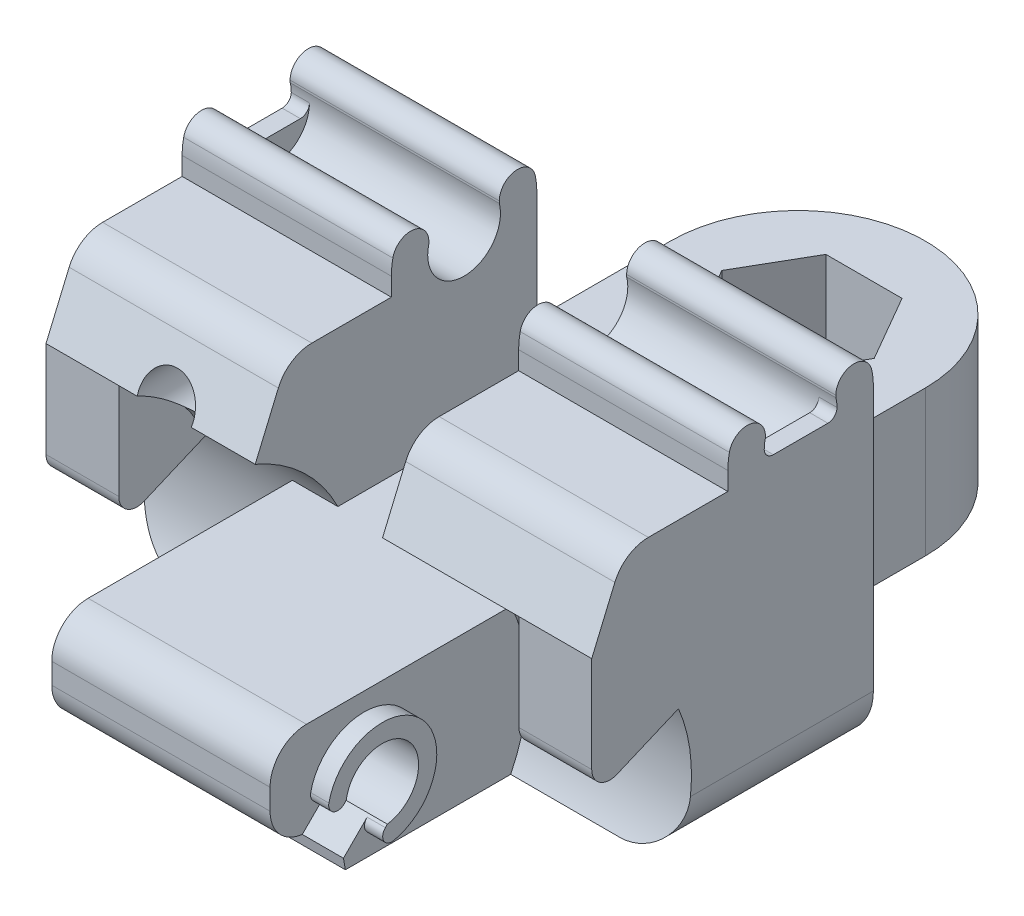
SolidWorks part; units mm, degrees
ref_plane "Front Plane" through (0, 0, 0) normal (0, 0, 1) x (1, 0, 0)
ref_plane "Top Plane" through (0, 0, 0) normal (0, 1, 0) x (1, 0, 0)
ref_plane "Right Plane" through (0, 0, 0) normal (1, 0, 0) x (0, 0, -1)
sketch "Sketch3" plane through (0, 0, 0) normal (1, 0, 0) x (0, 0, -1)
  line L0 (0.2828, -1.9799) -> (-1.9799, 0.2828)
  line L1 (0.2828, -1.9799) -> (-1.1314, -3.3941)
  line L2 (-1.1314, -3.3941) -> (-0.8188, -5.1668)
  line L3 (-0.8188, -5.1668) -> (-3.8071, -8.1551)
  line L4 (-1.9799, 0.2828) -> (-3.3941, -1.1314)
  line L5 (-3.3941, -1.1314) -> (-5.1668, -0.8188)
  line L6 (-5.1668, -0.8188) -> (-8.1551, -3.8071)
  line L7 (-0.8485, -0.8485) -> (0, 0) construction
  line L8 (0, 0) -> (-2, 0) construction
  line L9 (-1.9799, 0.2828) -> (-5.1668, -0.8188) construction
  line L10 (-0.8188, -5.1668) -> (0.2828, -1.9799) construction
  circle A0 centre (0, 0) radius 2
  circle A1 centre (0, 0) radius 8.5 construction
  circle A2 centre (0, 0) radius 9 construction
  circle A3 centre (0, 0) radius 9
  dimension "D1" = 4
  dimension "D2" = 17
  dimension "D3" = 7
  dimension "D4" = 0.5
  dimension "D5" = 2
  dimension "D7" = 3.2
  dimension "D6" = 1.8
  dimension "D8" = 45
  dimension "D9" = 125
extrude "Boss-Extrude1" add sketch "Sketch3" along normal mid plane 12 contours A3 L6 L5 L4 A0 L1 L2 L3 | A3 region at (0, -1.4772, -1.7032)
sketch "Sketch5" plane through (0, 0, 0) normal (1, 0, 0) x (0, 0, -1)
  line L0 (0, 9) -> (29.856, 9)
  line L1 (29.856, 9) -> (29.856, -9)
  line L2 (29.856, -9) -> (0, -9)
  arc A0 (-3.8071, -8.1551) -> (-8.1551, -3.8071) centre (0, 0) ccw construction
  arc A1 (0, -9) -> (0, 9) centre (0, 0) ccw
  dimension "D1" = 29.856
extrude "Boss-Extrude2" add sketch "Sketch5" along normal mid plane 14
sketch "Sketch6" plane through (0, 9, 0) normal (0, 1, 0) x (1, 0, 0)
  line L0 (7, 29.856) -> (-7, 29.856) construction
  circle A0 centre (0, 29.856) radius 7
extrude "Boss-Extrude3" add sketch "Sketch6" against normal up to surface (18 mm away) up to face at (0, -9, -9.952)
sketch "Sketch7" plane through (0, 0, 0) normal (0, 1, 0) x (1, 0, 0)
  circle A0 centre (0, 29.856) radius 4.5
  dimension "D1" = 9
extrude "Boss-Extrude4" add sketch "Sketch7" along normal blind 8 and the other way blind 8
sketch "Sketch8" plane through (0, 9, 0) normal (0, 1, 0) x (1, 0, 0)
  line L0 (6, -9) -> (6, 0) construction
  line L1 (-6, 0) -> (-6, -9) construction
  line L3 (7, 0) -> (7, 29.856) construction
  line L4 (-7, 29.856) -> (-7, 0) construction
  line L5 (-7, 0) -> (-6, 0) construction
  line L6 (6, 0) -> (7, 0) construction
  line L7 (6, -9) -> (6, 0)
  line L8 (-6, 0) -> (-6, -9)
  line L9 (-6, -9) -> (6, -9)
  line L10 (7, 0) -> (7, 29.856)
  line L11 (-7, 29.856) -> (-7, 0)
  line L12 (-7, 0) -> (-6, 0)
  line L13 (6, 0) -> (7, 0)
  arc A0 (7, 29.856) -> (-7, 29.856) centre (0, 29.856) ccw construction
  arc A1 (7, 29.856) -> (-7, 29.856) centre (0, 29.856) ccw
  line M10 (7, 0) -> (7, 29.856)
  arc M11 (7, 29.856) -> (-7, 29.856) centre (0, 29.856) ccw
  line M12 (-7, 29.856) -> (-7, 0)
  line M13 (-7, 0) -> (-6, 0)
  line M14 (-6, 0) -> (6, 0)
  line M15 (6, 0) -> (7, 0)
extrude "Cut-Extrude2" cut sketch "Sketch8" against normal offset from surface (5 mm away) 4 contours M15 M10 M11 M12 M13 M14 | L8 L9 L7 M14 region at (0, 9, 4.5) region at (0, 9, -17.7114) up to plane "Top Plane"
sketch "Sketch9" plane through (0, -9, 0) normal (0, -1, 0) x (1, 0, 0)
  line L7 (6, 0) -> (6, 9)
  line L8 (7, 0) -> (6, 0)
  line L9 (7, -29.856) -> (7, 0)
  line L10 (-7, 0) -> (-7, -29.856)
  line L11 (-6, 0) -> (-7, 0)
  line L12 (-6, 9) -> (-6, 0)
  line L13 (6, 9) -> (-6, 9)
  line L14 (6, 0) -> (6, 9)
  line L15 (7, 0) -> (6, 0)
  line L16 (7, -29.856) -> (7, 0)
  line L17 (-7, 0) -> (-7, -29.856)
  line L18 (-6, 0) -> (-7, 0)
  line L19 (-6, 9) -> (-6, 0)
  line L20 (6, 9) -> (-6, 9)
  arc A1 (-7, -29.856) -> (7, -29.856) centre (0, -29.856) ccw
  arc A2 (-7, -29.856) -> (7, -29.856) centre (0, -29.856) ccw
  line M10 (-7, 0) -> (-7, -29.856)
  arc M11 (-7, -29.856) -> (7, -29.856) centre (0, -29.856) ccw
  line M12 (7, -29.856) -> (7, 0)
  line M13 (7, 0) -> (6, 0)
  line M14 (6, 0) -> (-6, 0)
  line M15 (-6, 0) -> (-7, 0)
  dimension "D1" = 0
extrude "Cut-Extrude4" cut sketch "Sketch9" against normal offset from surface (5 mm away) 4 contours M15 M10 M11 M12 M13 M14 | L14 L20 L19 M14 region at (0, -9, 4.5) region at (0, -9, -17.7114) up to plane "Top Plane"
sketch "Sketch24" plane through (-6, 0, 0) normal (-1, 0, 0) x (0, 0, 1)
  line L0 (1.9799, 0.2828) -> (2.9258, -0.6631)
  line L1 (1.9799, 0.2828) -> (3.3941, -1.1314) construction
  line L2 (-0.2828, -1.9799) -> (0.6631, -2.9258)
  line L3 (-0.2828, -1.9799) -> (1.1314, -3.3941) construction
  arc A0 (1.9799, 0.2828) -> (-0.2828, -1.9799) centre (0, 0) ccw construction
  arc A1 (1.9799, 0.2828) -> (-0.2828, -1.9799) centre (0, 0) ccw
  circle A2 centre (0, 0) radius 3
  line M5 (1.1314, -3.3941) -> (-0.2828, -1.9799)
  arc M6 (-0.2828, -1.9799) -> (1.9799, 0.2828) centre (0, 0) cw
  line M7 (1.9799, 0.2828) -> (3.3941, -1.1314)
  dimension "D1" = 6
extrude "Boss-Extrude6" add sketch "Sketch24" along normal blind 1 contours A2 M7 M5 M6 region at (-6, 1.4742, -1.4742)
fillet "Fillet3" radius 0.5 2 edges at (-6.5, -2.9258, 0.6631) (-6.5, -0.6631, 2.9258)
mirror "Mirror1" about plane through (0, 0, 0) normal (1, 0, 0) of "Fillet3", "Boss-Extrude6"
sketch "Sketch10" plane through (0, 0, 0) normal (1, 0, 0) x (0, 0, -1)
  line L3 (8.0623, -4) -> (29.856, -4)
  line L4 (29.856, -4) -> (29.856, 4)
  line L5 (29.856, 4) -> (8.0623, 4)
  line L10 (11, 12.5) -> (11, 17.5) construction
  line L11 (11, 17.5) -> (19, 17.5) construction
  line L12 (19, 17.5) -> (19, 4) construction
  line L13 (5.3059, 12.5) -> (11, 12.5)
  line L14 (0, 0) -> (3.5166, 8.2845) construction
  line L15 (3.5166, 8.2845) -> (5.3059, 12.5)
  line L16 (29.856, 4) -> (8.0623, 4) construction
  line L17 (19, 4) -> (8.0623, 4)
  line L18 (11, 13.5) -> (19, 13.5) construction
  line L19 (29, 14) -> (29, 4) construction
  line L20 (29.856, -4) -> (8.0623, -4) construction
  line L21 (13.0635, 14) -> (16.9365, 14) construction
  line L22 (16.9365, 14) -> (16.9365, 17)
  line L23 (13.0635, 17) -> (13.0635, 14)
  line L24 (11, 13.5) -> (11, 12.5)
  line L25 (19, 13.5) -> (19, 4)
  line L26 (19, -4) -> (8.0623, -4)
  line L27 (19, 4) -> (19, -4)
  arc A0 (13.0635, 14) -> (16.9365, 14) centre (15, 13.5) ccw
  arc A1 (8.0623, -4) -> (8.0623, 4) centre (0, 0) ccw
  arc A2 (8.0623, 4) -> (3.5166, 8.2845) centre (0, 0) ccw
  arc A3 (19, 13.5) -> (16.9365, 17) centre (15, 13.5) ccw
  arc A4 (13.0635, 17) -> (11, 13.5) centre (15, 13.5) ccw
  arc A5 (8.0623, -4) -> (8.0623, 4) centre (0, 0) ccw construction
  arc A6 (8.0623, -4) -> (8.0623, 4) centre (0, 0) ccw
  dimension "D8" = 4
  dimension "D9" = 2
  dimension "D10" = 2.5
  dimension "D2" = 67
  dimension "D3" = 10
  dimension "D4" = 13.5
  dimension "D5" = 5
  dimension "D6" = 15
  dimension "D7" = 5
  dimension "D1" = 0
extrude "Boss-Extrude5" add sketch "Sketch10" along normal mid plane 30 contours A6 L26 L27 L17 | L23 A4 L24 L13 L15 A2 L17 L25 A3 L22 A0 region at (0, 0, -13.8434) region at (0, 9.0287, -12.3917)
ref_plane "Plane1" through (6, 0, 0) normal (1, 0, 0) x (0, 0, -1)
ref_plane "Plane2" through (-6, 0, 0) normal (1, 0, 0) x (0, 0, -1)
sketch "Sketch13" plane through (-6, 0, 0) normal (1, 0, 0) x (0, 0, -1)
  line L0 (0, 5) -> (36.856, 5)
  line L2 (36.856, 4) -> (36.856, 5) construction
  circle A0 centre (0, 0) radius 5 construction
  dimension "D1" = 10
ref_plane "Plane3" through (0, 0, 0) normal (0, 0, 1) x (1, 0, 0)
ref_plane "Plane4" [suppressed] through (0, 0, -32.856) normal (0, 0, -1) x (-1, 0, 0)
ref_plane "Plane5" [suppressed] through (-3, 0, 0) normal (-1, 0, 0) x (0, 0, 1)
sketch "Sketch18" [suppressed] plane through (0, 0, -32.856) normal (0, 0, -1) x (-1, 0, 0)
  line L0 (0, 29) -> (0, 16) construction
  line L2 (3, 29) -> (-3, 29) construction
  circle A0 centre (0, 16) radius 1.9
  dimension "D2" = 3.8
  dimension "D1" = 13
extrude "Cut-Extrude5" [suppressed] cut sketch "Sketch18" against normal blind 1
sketch "Sketch20" plane through (0, 4, 0) normal (0, 1, 0) x (1, 0, 0)
  line L0 (0, 25.356) -> (0, 0) construction
  line L2 (-3.5, -19) -> (3.5, -19)
  line L3 (-3.5, -19) -> (-3.5, 19)
  line L4 (-3.5, 19) -> (3.5, 19)
  line L5 (3.5, -19) -> (3.5, 19)
  line L6 (-3.5, -19) -> (3.5, 19) construction
  line L7 (-3.5, 19) -> (3.5, -19) construction
  line L8 (-7, 19) -> (7, 19) construction
  dimension "D1" = 7
extrude "Cut-Extrude7" cut sketch "Sketch20" along normal through all
sketch "Sketch32" plane through (6, 0, 0) normal (1, 0, 0) x (0, 0, -1)
  line L0 (-5.1668, -0.8188) -> (-5.1668, 4)
  line L1 (8.0623, 4) -> (-8.0623, 4) construction
  line L9 (-3.3941, -1.1314) -> (-2.0905, 0.1722)
  line L10 (0.1722, -2.0905) -> (-1.1314, -3.3941)
  line L11 (-1.1314, -3.3941) -> (-1.0245, -4)
  line L12 (-1.0245, -4) -> (8.0623, -4)
  line L13 (8.0623, 4) -> (-8.0623, 4)
  line L14 (-8.1551, -3.8071) -> (-5.1668, -0.8188)
  line L15 (-5.1668, -0.8188) -> (-3.3941, -1.1314)
  line L16 (-3.3941, -1.1314) -> (-2.0905, 0.1722)
  line L17 (0.1722, -2.0905) -> (-1.1314, -3.3941)
  line L18 (-1.1314, -3.3941) -> (-1.0245, -4)
  line L19 (-1.0245, -4) -> (8.0623, -4)
  line L20 (8.0623, 4) -> (-8.0623, 4)
  line L21 (-8.1551, -3.8071) -> (-5.1668, -0.8188)
  line L22 (-5.1668, -0.8188) -> (-3.3941, -1.1314)
  arc A5 (-2.9329, 0.6309) -> (-2.0905, 0.1722) centre (-2.4441, 0.5258) ccw
  arc A6 (0.6309, -2.9329) -> (-2.9329, 0.6309) centre (0, 0) ccw
  arc A7 (0.1722, -2.0905) -> (0.6309, -2.9329) centre (0.5258, -2.4441) ccw
  arc A8 (8.0623, -4) -> (8.0623, 4) centre (0, 0) ccw
  arc A9 (-8.0623, 4) -> (-8.1551, -3.8071) centre (0, 0) ccw
  arc A10 (-2.9329, 0.6309) -> (-2.0905, 0.1722) centre (-2.4441, 0.5258) ccw
  arc A11 (0.6309, -2.9329) -> (-2.9329, 0.6309) centre (0, 0) ccw
  arc A12 (0.1722, -2.0905) -> (0.6309, -2.9329) centre (0.5258, -2.4441) ccw
  arc A13 (8.0623, -4) -> (8.0623, 4) centre (0, 0) ccw
  arc A14 (-8.0623, 4) -> (-8.1551, -3.8071) centre (0, 0) ccw
  line M21 (8.0623, 4) -> (-8.0623, 4)
  arc M22 (-8.0623, 4) -> (-8.1551, -3.8071) centre (0, 0) ccw
  line M23 (-8.1551, -3.8071) -> (-5.1668, -0.8188)
  dimension "D1" = 0
extrude "Cut-Extrude9" cut sketch "Sketch32" against normal blind 25 contours L0 M23 M21 M22 region at (6, 0.6368, 7.0987)
fillet "Fillet1" radius 2 2 edges at (0, 4, 5.1668) (0, -0.8188, 5.1668)
fillet "Fillet2" radius 1 4 edges at (-9.25, 17, -16.9365) (-9.25, 17, -13.0635) (9.25, 17, -13.0635) (9.25, 17, -16.9365)
sketch "Sketch23" plane through (0, 4, 0) normal (0, 1, 0) x (1, 0, 0)
  line L0 (-7, 29.856) -> (7, 29.856) construction
  line L1 (4.1881, 29.856) -> (2.094, 33.483)
  line L2 (2.094, 33.483) -> (-2.094, 33.483)
  line L3 (-2.094, 33.483) -> (-4.1881, 29.856)
  line L4 (-4.1881, 29.856) -> (-2.094, 26.229)
  line L5 (-2.094, 26.229) -> (2.094, 26.229)
  line L6 (2.094, 26.229) -> (4.1881, 29.856)
  line L7 (-7, 19) -> (-7, 29.856) construction
  circle A0 centre (0, 29.856) radius 3.627 construction
  dimension "D1" = 7.254
extrude "Cut-Extrude8" cut sketch "Sketch23" against normal through all
sketch "Sketch25" plane through (15, 0, 0) normal (1, 0, 0) x (0, 0, -1)
  line L0 (13.0635, 13) -> (16.9365, 13)
  arc A0 (13.0635, 14) -> (16.9365, 14) centre (15, 13.5) ccw construction
  arc A1 (13.0635, 14) -> (16.9365, 14) centre (15, 13.5) ccw
  arc M14 (16.9365, 14) -> (13.0635, 14) centre (15, 13.5) cw
  dimension "D1" = 1.5
extrude "Boss-Extrude7" add sketch "Sketch25" against normal blind 1 contours L0 M14 region at (15, 12.3752, -15)
fillet "Fillet4" radius 0.5 2 edges at (14.5, 13, -16.9365) (14.5, 13, -13.0635)
mirror "Mirror2" about plane through (0, 0, 0) normal (1, 0, 0) of "Fillet4", "Boss-Extrude7"
fillet "Fillet5" radius 3 2 edges at (15, -4, -13.5311) (-15, -4, -13.5311)
fillet "Fillet7" radius 2 2 edges at (-9.25, 12.5, -5.3059) (9.25, 12.5, -5.3059)
ref_plane "Plane6" through (-8.5, 0, 0) normal (-1, 0, 0) x (0, 0, 1)
sketch "Sketch27" plane through (-8.5, 0, 0) normal (-1, 0, 0) x (0, 0, 1)
  line L0 (0, 8.5) -> (-25.4214, 8.5)
  circle A0 centre (0, 0) radius 8.5 construction
  dimension "D1" = 17
sweep "Cut-Sweep1" cut path "Sketch27" circular profile diameter 3 parameters "D3"=3
sketch "Sketch28" plane through (15, 0, 0) normal (1, 0, 0) x (0, 0, -1)
  line L0 (0, 0) -> (8.2845, 3.5166) construction
  line L1 (8.2845, 3.5166) -> (3.5166, 1.4927)
  line L2 (0, 0) -> (0, 8.2854) construction
  line L3 (3.5166, 1.4927) -> (3.5166, 8.2845)
  arc A0 (8.9443, -1) -> (3.5166, 8.2845) centre (0, 0) ccw construction
  arc A1 (8.9443, -1) -> (3.5166, 8.2845) centre (0, 0) ccw
  arc M6 (3.5166, 8.2845) -> (8.9443, -1) centre (0, 0) cw
  dimension "D1" = 67
extrude "Boss-Extrude8" add sketch "Sketch28" against normal blind 4 contours L3 L1 M6 region at (15, 4.6877, -5.2578)
fillet "Fillet8" radius 1 1 edges at (13, 1.4927, -3.5166)
mirror "Mirror3" about plane through (0, 0, 0) normal (1, 0, 0) of "Fillet8", "Boss-Extrude8"
